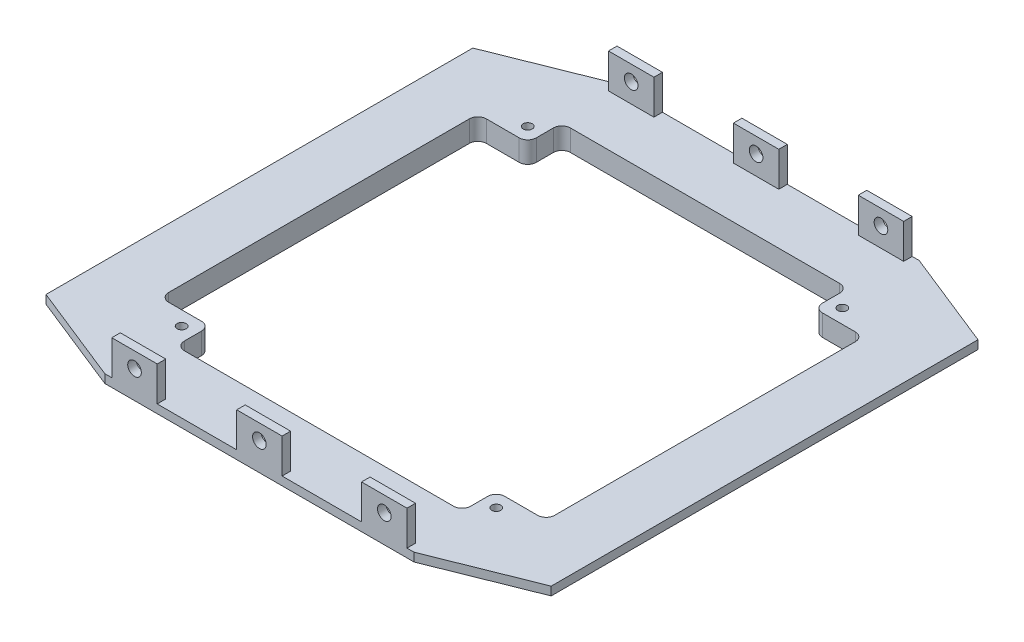
SolidWorks part; units mm, degrees
material "6061-T6 (SS)"
ref_plane "Front Plane" through (0, 0, 0) normal (0, 0, 1) x (1, 0, 0)
ref_plane "Top Plane" through (0, 0, 0) normal (0, 1, 0) x (1, 0, 0)
ref_plane "Right Plane" through (0, 0, 0) normal (1, 0, 0) x (0, 0, -1)
sketch "Sketch1" plane through (0, 0, 0) normal (0, 1, 0) x (1, 0, 0)
  line L5 (-35.5, 0) -> (0, 0) construction
  line L6 (-25.5, -35.5) -> (25.5, -35.5)
  line L10 (-35.5, -31.5) -> (-35.5, 31.5)
  line L11 (-25.5, 35.5) -> (25.5, 35.5)
  line L12 (35.5, -31.5) -> (35.5, 31.5)
  line L13 (0, 0) -> (0, 35.5) construction
  line L14 (25.5, -35.5) -> (35.5, -31.5)
  line L15 (25.5, 35.5) -> (35.5, 31.5)
  line L16 (-25.5, -35.5) -> (-35.5, -31.5)
  line L17 (-25.5, 35.5) -> (-35.5, 31.5)
  point P0 (0, 0)
  point P4 (35.5, -35.5)
  dimension "D3" = 4
  dimension "D2" = 10
  dimension "D4" = 71
extrude "Boss-Extrude1" add sketch "Sketch1" along normal mid plane 4.5
sketch "Sketch2" plane through (0, 2.25, 0) normal (0, 1, 0) x (1, 0, 0)
  line L16 (27.2332, -44.5) -> (44.5, -37.5933)
  line L17 (44.5, -37.5933) -> (44.5, 37.5933)
  line L18 (44.5, 37.5933) -> (27.2332, 44.5)
  line L19 (27.2332, 44.5) -> (-27.2332, 44.5)
  line L20 (-27.2332, 44.5) -> (-44.5, 37.5933)
  line L21 (-44.5, 37.5933) -> (-44.5, -37.5933)
  line L22 (-44.5, -37.5933) -> (-27.2332, -44.5)
  line L23 (-27.2332, -44.5) -> (27.2332, -44.5)
  line L24 (27.2332, -44.5) -> (44.5, -37.5933)
  line L25 (44.5, -37.5933) -> (44.5, 37.5933)
  line L26 (44.5, 37.5933) -> (27.2332, 44.5)
  line L27 (27.2332, 44.5) -> (-27.2332, 44.5)
  line L28 (-27.2332, 44.5) -> (-44.5, 37.5933)
  line L29 (-44.5, 37.5933) -> (-44.5, -37.5933)
  line L30 (-44.5, -37.5933) -> (-27.2332, -44.5)
  line L31 (-27.2332, -44.5) -> (27.2332, -44.5)
  dimension "D1" = 9
extrude "Boss-Extrude2" add sketch "Sketch2" along normal blind 1.5
mirror "Mirror1" about plane through (0, 0, 0) normal (0, 1, 0) of "Boss-Extrude2"
sketch "Sketch3" plane through (0, 0, 0) normal (0, 1, 0) x (1, 0, 0)
  line L16 (-25.2111, -34) -> (25.2111, -34)
  line L17 (25.2111, -34) -> (34, -30.4845)
  line L18 (34, -30.4845) -> (34, 30.4845)
  line L19 (34, 30.4845) -> (25.2111, 34)
  line L20 (25.2111, 34) -> (-25.2111, 34)
  line L21 (-25.2111, 34) -> (-34, 30.4845)
  line L22 (-34, 30.4845) -> (-34, -30.4845)
  line L23 (-34, -30.4845) -> (-25.2111, -34)
  line L24 (-25.2111, -34) -> (25.2111, -34)
  line L25 (25.2111, -34) -> (34, -30.4845)
  line L26 (34, -30.4845) -> (34, 30.4845)
  line L27 (34, 30.4845) -> (25.2111, 34)
  line L28 (25.2111, 34) -> (-25.2111, 34)
  line L29 (-25.2111, 34) -> (-34, 30.4845)
  line L30 (-34, 30.4845) -> (-34, -30.4845)
  line L31 (-34, -30.4845) -> (-25.2111, -34)
  dimension "D1" = 10.5
extrude "Cut-Extrude1" cut sketch "Sketch3" against normal through all both and the other way through all
sketch "Sketch5" plane through (0, 0, 0) normal (0, 0, 1) x (1, 0, 0)
  line L0 (0, 0) -> (0, 9.85) construction
  line L1 (-27.2332, 3.75) -> (27.2332, 3.75) construction
  line L2 (-26, 3.75) -> (-18, 3.75)
  line L3 (-26, 3.75) -> (-26, 9.85)
  line L4 (-26, 9.85) -> (-18, 9.85)
  line L5 (-18, 3.75) -> (-18, 9.85)
  line L6 (-22, 9.85) -> (-22, 3.75) construction
  line L11 (4, 9.85) -> (-4, 9.85)
  line L12 (-4, 9.85) -> (-4, 3.75)
  line L13 (-4, 3.75) -> (4, 3.75)
  line L14 (22, 9.85) -> (22, 3.75) construction
  line L15 (4, 9.85) -> (4, 3.75)
  line L16 (18, 3.75) -> (18, 9.85)
  line L17 (26, 9.85) -> (18, 9.85)
  line L18 (26, 3.75) -> (26, 9.85)
  line L19 (26, 3.75) -> (18, 3.75)
  point P19 (0, 3.75)
  dimension "D1" = 22
  dimension "D3" = 6.1
  dimension "D2" = 8
  dimension "D4" = 8
extrude "Boss-Extrude3" add sketch "Sketch5" against normal blind 1.5 from surface starting at face at (0, 3, 44.5)
extrude "Boss-Extrude4" add sketch "Sketch5<2>" along normal blind 1.5 from surface starting at face at (0, 3, -44.5)
sketch "Sketch5<2>" plane through (0, 0, 0) normal (0, 0, 1) x (1, 0, 0) same geometry as "Sketch5"
sketch "Sketch6" plane through (0, 0, 0) normal (0, 0, 1) x (1, 0, 0)
  line L0 (-22, 9.85) -> (-22, 7.15) construction
  line L1 (-18, 9.85) -> (-26, 9.85) construction
  line L2 (0, 0) -> (0, 7.15) construction
  line L3 (-22, 7.15) -> (-22, 1.75) construction
  line L4 (-22, 7.15) -> (22, 7.15) construction
  line L5 (-22, 1.75) -> (22, 1.75) construction
  line L6 (22, 7.15) -> (22, 1.75) construction
  line L7 (22, 9.85) -> (22, 7.15) construction
  circle A0 centre (-22, 7.15) radius 1.2
  circle A2 centre (-22, 1.75) radius 1.2
  circle A4 centre (0, 7.15) radius 1.2
  circle A5 centre (0, 1.75) radius 1.2
  circle A6 centre (22, 1.75) radius 1.2
  circle A7 centre (22, 7.15) radius 1.2
  dimension "D1" = 2.4
  dimension "D2" = 2.7
  dimension "D3" = 5.4
extrude "Cut-Extrude3" [suppressed] cut sketch "Sketch6" against normal through all both and the other way through all
sketch "Sketch7" plane through (0, 0, 0) normal (0, 1, 0) x (1, 0, 0)
  line L0 (44.5, -37.5933) -> (44.5, 37.5933) construction
  line L1 (-44.5, 44.5) -> (44.5, 44.5)
  line L2 (-44.5, 44.5) -> (-44.5, -44.5)
  line L3 (-44.5, -44.5) -> (44.5, -44.5)
  line L4 (44.5, 44.5) -> (44.5, -44.5)
  line L5 (-44.5, 44.5) -> (44.5, -44.5) construction
  line L6 (-44.5, -44.5) -> (44.5, 44.5) construction
  line L8 (-18, -44.5) -> (-4, -44.5) construction
  point P1 (0, 0)
extrude "Cut-Extrude4" cut sketch "Sketch7" against normal through all
sketch "Sketch8" plane through (0, 0, 0) normal (0, 1, 0) x (1, 0, 0)
  line L0 (-25.2111, -34) -> (-34, -30.4845)
  line L1 (-34, -30.4845) -> (-34, -27.9845)
  line L2 (-34, 30.4845) -> (-34, -30.4845) construction
  line L3 (-34, -27.9845) -> (-25.2111, -27.9845)
  line L4 (-25.2111, -27.9845) -> (-25.2111, -34)
  line L6 (0, -44.5) -> (0, 44.5) construction
  line L7 (-44.5, 0) -> (44.5, 0) construction
  line L8 (44.5, -37.5933) -> (44.5, 37.5933) construction
  line L9 (-34, -30.4845) -> (-25.2111, -30.4845) construction
  line L10 (34, 30.4845) -> (25.2111, 30.4845) construction
  line L15 (34, -30.4845) -> (25.2111, -30.4845) construction
  line L16 (-34, 30.4845) -> (-25.2111, 30.4845) construction
  line L21 (-25.2111, 27.9845) -> (-25.2111, 34)
  line L22 (-34, 27.9845) -> (-25.2111, 27.9845)
  line L23 (-34, 30.4845) -> (-34, 27.9845)
  line L24 (-25.2111, 34) -> (-34, 30.4845)
  line L25 (25.2111, 34) -> (34, 30.4845)
  line L26 (34, 30.4845) -> (34, 27.9845)
  line L27 (4, -44.5) -> (18, -44.5) construction
  line L28 (18, 44.5) -> (4, 44.5) construction
  line L29 (34, 27.9845) -> (25.2111, 27.9845)
  line L30 (25.2111, 27.9845) -> (25.2111, 34)
  line L31 (25.2111, -27.9845) -> (25.2111, -34)
  line L32 (34, -27.9845) -> (25.2111, -27.9845)
  line L33 (34, -30.4845) -> (34, -27.9845)
  line L34 (25.2111, -34) -> (34, -30.4845)
  point P4 (-27.7111, -30.4845)
  point P11 (0, 0)
  point P14 (0, 0)
  point P20 (0, 0)
  point P22 (0, 0)
  point P34 (-27.7111, 30.4845)
  point P37 (0, 0)
  point P44 (27.7111, 30.4845)
  point P45 (27.7111, -30.4845)
  dimension "D2" = 2.5
  dimension "D1" = 2.5
extrude "Boss-Extrude5" add sketch "Sketch8" along normal up to surface (3.75 mm away) up to face at (0, 3.75, 0)
fillet "Fillet2" radius 1.5 12 edges at (-34, 1.875, 27.9845) (-25.2111, 1.875, 34) (-34, 1.875, -27.9845) (-25.2111, 1.875, -34) (-25.2111, 1.875, -27.9845) (-25.2111, 1.875, 27.9845) (25.2111, 1.875, -27.9845) (25.2111, 1.875, -34) (34, 1.875, -27.9845) (34, 1.875, 27.9845) (25.2111, 1.875, 34) (25.2111, 1.875, 27.9845)
hole_wizard "M2x0.4 Tapped Hole1" positions "Sketch11" profile "Sketch12" tap size "M2x0.4" standard "ANSI Metric" end condition through all
sketch "Sketch11" plane through (0, 3.75, 0) normal (0, 1, 0) x (1, 0, 0)
  point P0 (-27.7111, 30.4845)
  point P3 (27.7111, 30.4845)
  point P6 (27.7111, -30.4845)
  point P9 (-27.7111, -30.4845)
  point P12 (0, 0)
  point P13 (0, 0)
  point P14 (0, 0)
  point P15 (0, 0)
  point P17 (0, 0)
sketch "Sketch12" plane through (-27.7111, 3.75, -30.4845) normal (1, 0, 0) x (0, 0, 1)
  line L0 (0, 0) -> (0, 3.75)
  line L1 (0, 3.75) -> (0.8, 3.75)
  line L2 (0.8, 3.75) -> (0.8, 0)
  line L5 (0.8, 0) -> (0, 0)
  line L11 (0, -6.35) -> (0, 107.95) construction
  dimension "Thru Tap Drill Dia." = 1.6
  dimension "Thru Tap Drill Depth" = 3.75
cosmetic thread "Hole Thread1" parameters "D2"=2
cosmetic thread "Hole Thread2" parameters "D2"=2
cosmetic thread "Hole Thread3" parameters "D2"=2
cosmetic thread "Hole Thread4" parameters "D2"=2
extrude "3U Hole cutthrough" cut sketch "Sketch6<2>" against normal through all both and the other way through all contours A0 | A4 | A7 region at (-22, 7.15, 0) region at (0, 7.15, 0) region at (22, 7.15, 0)
sketch "Sketch6<2>" plane through (0, 0, 0) normal (0, 0, 1) x (1, 0, 0) same geometry as "Sketch6"
